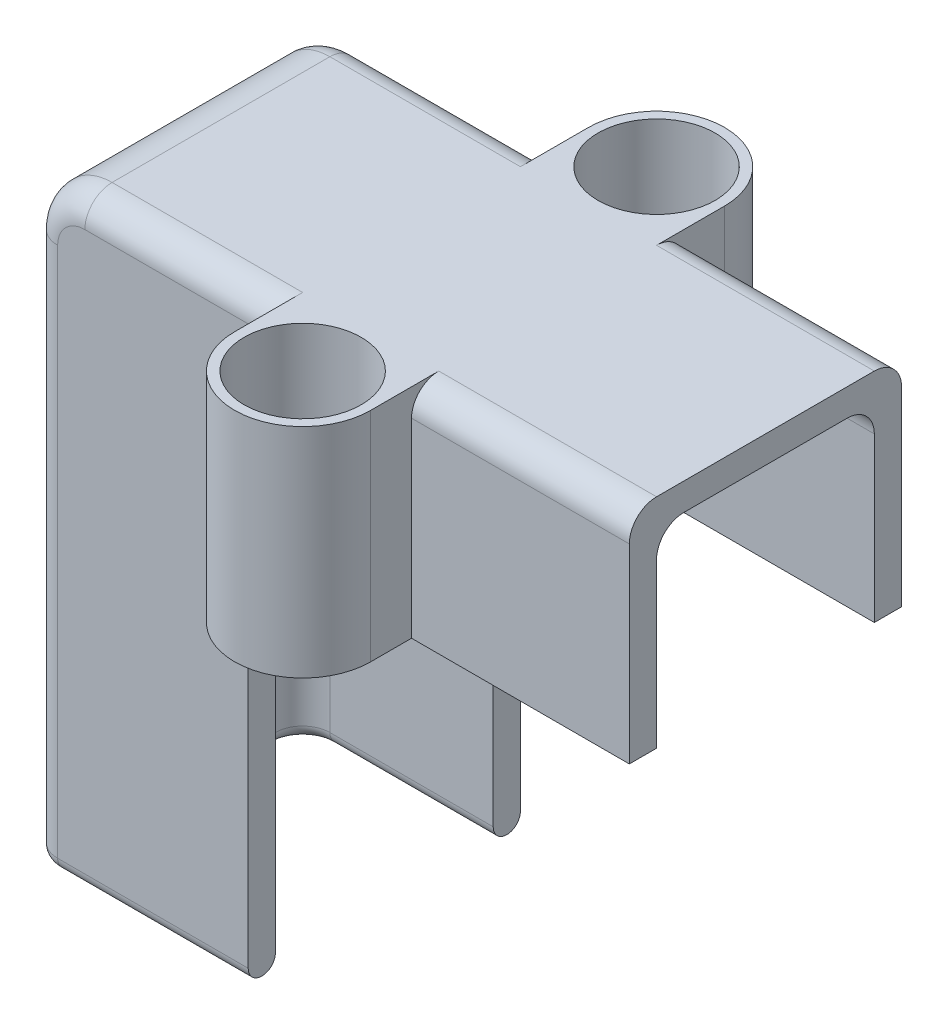
SolidWorks part; units mm, degrees
material "PLA MATTE"
ref_plane "前视基准面" through (0, 0, 0) normal (0, 0, 1) x (1, 0, 0)
ref_plane "上视基准面" through (0, 0, 0) normal (0, 1, 0) x (1, 0, 0)
ref_plane "右视基准面" through (0, 0, 0) normal (1, 0, 0) x (0, 0, -1)
sketch "草图1" plane through (0, 0, 0) normal (0, 0, 1) x (1, 0, 0)
  line L0 (0, 0) -> (18, 0)
  line L1 (0, 0) -> (0, -18)
  dimension "D1" = 18
  dimension "D2" = 18
extrude "拉伸-薄壁1" add sketch "草图1" along normal mid plane 10 thin thin type mid plane wall 8
sketch "草图3" plane through (0, 4, 0) normal (0, 1, 0) x (1, 0, 0)
  line L0 (18, 0) -> (7.5, 0) construction
  line L1 (18, -5) -> (18, 5) construction
  line L2 (7.5, 6.5) -> (7.5, -6.5) construction
  line L3 (10, 6.5) -> (10, -6.5)
  line L4 (5, 6.5) -> (5, -6.5)
  arc A0 (10, 6.5) -> (5, 6.5) centre (7.5, 6.5) ccw
  arc A1 (5, -6.5) -> (10, -6.5) centre (7.5, -6.5) ccw
  point P7 (7.5, 0)
  dimension "D1" = 10.5
  dimension "D2" = 5
  dimension "D3" = 13
extrude "凸台-拉伸1" add sketch "草图3" against normal up to surface (8 mm away) up to face at (11, -4, 0)
sketch "草图2" plane through (0, 0, 0) normal (0, 0, 1) x (1, 0, 0)
  line L0 (-4, 4) -> (-4, -18) construction
  line L2 (-4, 4) -> (-4, -18) construction
  line L3 (17, 4) -> (-4, 4) construction
  line L4 (18, 3) -> (-3, 3)
  line L5 (-3, 3) -> (-3, -18)
  line L6 (18, 3) -> (18, -4)
  line L7 (18, -4) -> (4, -4)
  line L8 (4, -4) -> (4, -18)
  line L9 (4, -18) -> (-3, -18)
  dimension "D2" = 1
  dimension "D1" = 1
extrude "切除-拉伸1" cut sketch "草图2" against normal mid plane 8
fillet "圆角1" radius 2 2 edges at (-4, 4, 0) (-3, 3, 0)
hole_wizard "打孔尺寸(%根据)内六角圆柱头螺钉的类型1" positions "草图7" profile "草图8" counterbore size "M2" standard "GB"
sketch "草图7" plane through (0, 4, 0) normal (0, 1, 0) x (1, 0, 0)
  point P0 (7.5, 6.5)
  point P3 (7.5, -6.5)
sketch "草图8" plane through (7.5, 4, -6.5) normal (1, 0, 0) x (0, 0, 1)
  line L0 (0, 0) -> (0, 15.721)
  line L1 (0, 15.721) -> (1.2, 15)
  line L2 (1.2, 15) -> (1.2, 5)
  line L3 (1.2, 5) -> (2.15, 5)
  line L4 (2.15, 5) -> (2.15, 0)
  line L5 (2.15, 0) -> (0, 0)
  line L10 (0, 15.721) -> (-1.2, 15) construction
  line L11 (0, -6.35) -> (0, 107.95) construction
  dimension "孔直径" = 2.4
  dimension "孔深度" = 15
  dimension "柱形沉头孔直径" = 4.3
  dimension "柱形沉头孔深度" = 5
  dimension "导头角度" = 118
fillet "圆角2" radius 1 12 edges at (1.5, 4, -5) (-3.4142, 3.4142, -5) (1.5, 4, 5) (-4, -8, 5) (8.5, 3, 4) (-2.4142, 2.4142, 4) (8.5, 3, -4) (-2.4142, 2.4142, -4) (-4, -8, -5) (-3.4142, 3.4142, 5) (-3, -8.5, 4) (-3, -8.5, -4)
fillet "圆角3" radius 1 2 edges at (14, 4, 5) (14, 4, -5)
fillet "圆角4" radius 1 2 edges at (4, -4, -4.5) (4, -4, 4.5)
fillet "圆角5" radius 0.5 5 edges at (0.5, -18, 5) (-3.7071, -18, 4.7071) (0.5, -18, -5) (-3.7071, -18, -4.7071) (-4, -18, 0)
fillet "圆角6" radius 0.5 5 edges at (1, -18, -4) (-2.7071, -18, -3.7071) (1, -18, 4) (-2.7071, -18, 3.7071) (-3, -18, 0)
